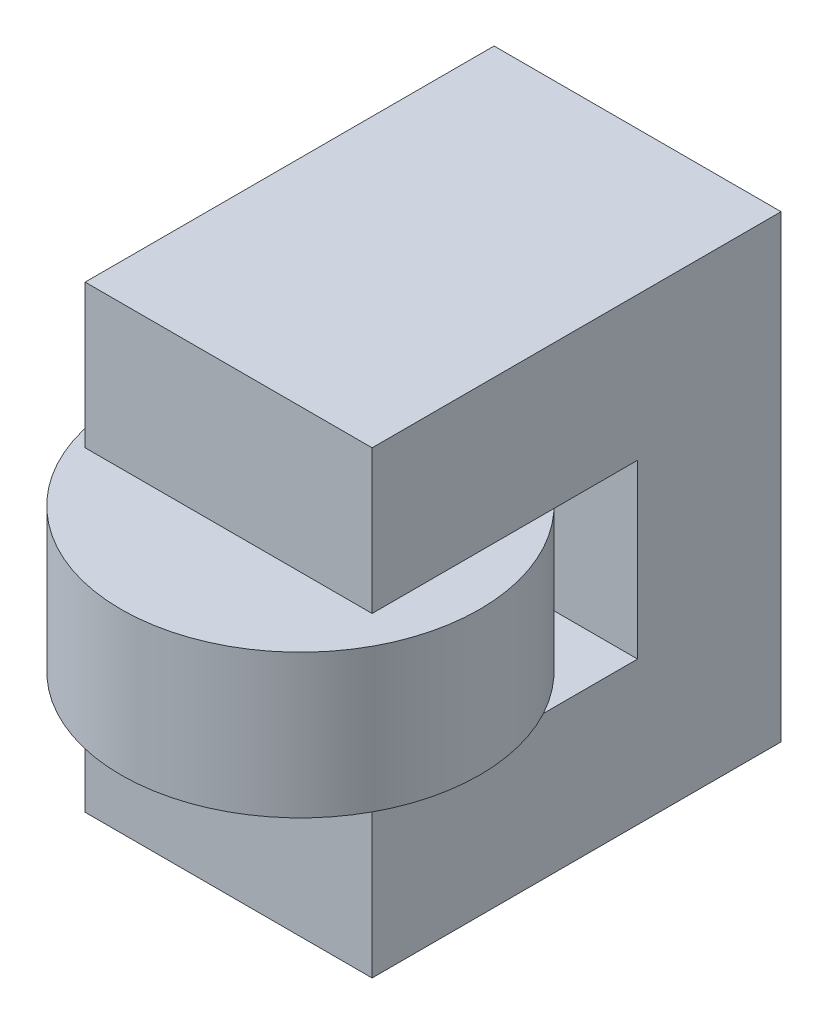
SolidWorks part; units mm, degrees
ref_plane "Front Plane" through (0, 0, 0) normal (0, 0, 1) x (1, 0, 0)
ref_plane "Top Plane" through (0, 0, 0) normal (0, 1, 0) x (1, 0, 0)
ref_plane "Right Plane" through (0, 0, 0) normal (1, 0, 0) x (0, 0, -1)
sketch "Sketch1" plane through (0, 0, 0) normal (0, 1, 0) x (1, 0, 0)
  circle A0 centre (0, 0) radius 12.5
  dimension "D1" = 25
extrude "Boss-Extrude1" add sketch "Sketch1" along normal blind 10 contours A0
hole_wizard "#8 Clearance Hole1" positions "Sketch2" profile "Sketch3" hole size "#8" standard "ANSI Inch" end condition through all
sketch "Sketch2" plane through (0, 0, 0) normal (0, -1, 0) x (-1, 0, 0)
  point P0 (0, 0)
sketch "Sketch3" plane through (0, 0, 0) normal (1, 0, 0) x (0, 0, -1)
  line L0 (0, 0) -> (0, 10)
  line L1 (0, 10) -> (2.4574, 10)
  line L2 (2.4574, 10) -> (2.4574, 0)
  line L5 (2.4574, 0) -> (0, 0)
  line L11 (0, -6.35) -> (0, 107.95) construction
  dimension "Thru Hole Dia." = 4.9149
  dimension "Thru Hole Depth" = 10
ref_plane "midplane reference" through (0, 5, 0) normal (0, 1, 0) x (1, 0, 0)
sketch "Sketch4" plane through (0, 0, 0) normal (1, 0, 0) x (0, 0, -1)
  line L11 (-5, -1) -> (13.5, -1)
  line L12 (13.5, -1) -> (13.5, 11)
  line L14 (23.5, 21) -> (23.5, -11)
  line L15 (23.5, -11) -> (-5, -11)
  line L16 (-5, -11) -> (-5, -1)
  line L18 (13.75, 5) -> (-13.75, 5) construction
  line L19 (-5, 21) -> (-5, 11)
  line L20 (23.5, 21) -> (-5, 21)
  line L21 (-5, 11) -> (13.5, 11)
  line L23 (-12.5, 0) -> (12.5, 0) construction
  line L24 (12.5, 0) -> (12.5, 10) construction
  dimension "D1" = 10
  dimension "D2" = 10
  dimension "D3" = 1
  dimension "D4" = 5
  dimension "D5" = 1
extrude "Boss-Extrude2" add sketch "Sketch4" along normal blind 10 and the other way blind 10 separate body
